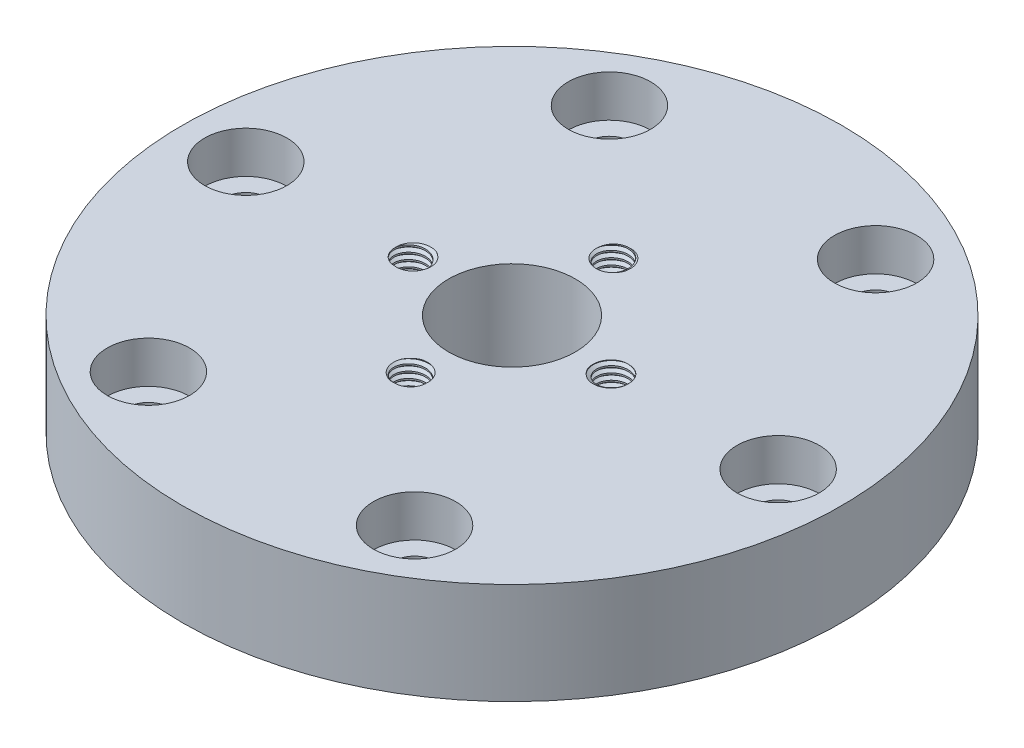
SolidWorks part; units mm, degrees
ref_plane "Front Plane" through (0, 0, 0) normal (0, 0, 1) x (1, 0, 0)
ref_plane "Top Plane" through (0, 0, 0) normal (0, 1, 0) x (1, 0, 0)
ref_plane "Right Plane" through (0, 0, 0) normal (1, 0, 0) x (0, 0, -1)
sketch "Sketch1" plane through (0, 0, 0) normal (0, 1, 0) x (1, 0, 0)
  circle A0 centre (0, 0) radius 5
  circle A1 centre (0, 0) radius 26
  dimension "D1" = 10
  dimension "D2" = 52
extrude "Boss-Extrude1" add sketch "Sketch1" along normal blind 8
sketch "Sketch2" plane through (0, 8, 0) normal (0, 1, 0) x (1, 0, 0)
  line L0 (0, 0) -> (0, 8) construction
  line L1 (0, 0) -> (-21, 0) construction
  circle A0 centre (0, 8) radius 1.25
  circle A1 centre (-21, 0) radius 1.7
  circle A2 centre (8, 0) radius 1.25
  circle A4 centre (0, -8) radius 1.25
  circle A6 centre (-8, 0) radius 1.25
  circle A8 centre (0, 21) radius 1.7 [skipped]
  circle A9 centre (21, 0) radius 1.7 [skipped]
  circle A10 centre (0, -21) radius 1.7 [skipped]
  circle A11 centre (-10.5, 18.1865) radius 1.7
  circle A12 centre (10.5, 18.1865) radius 1.7
  circle A13 centre (21, 0) radius 1.7
  circle A14 centre (10.5, -18.1865) radius 1.7
  circle A15 centre (-10.5, -18.1865) radius 1.7
  point P21 (0, 0)
  point P32 (0, 0)
  dimension "D3" = 2.5
  dimension "D4" = 3.4
  dimension "D1" = 21
  dimension "D2" = 8
  dimension "D5" = 4
  dimension "D6" = 6
extrude "Cut-Extrude1" cut sketch "Sketch2" against normal through all
sketch "Sketch3" plane through (0, 8, 0) normal (0, 1, 0) x (1, 0, 0)
  circle A0 centre (-21, 0) radius 3.25
  circle A1 centre (-10.5, 18.1865) radius 3.25
  circle A2 centre (10.5, 18.1865) radius 3.25
  circle A3 centre (21, 0) radius 3.25
  circle A4 centre (10.5, -18.1865) radius 3.25
  circle A5 centre (-10.5, -18.1865) radius 3.25
  point P15 (0, 0)
  dimension "D1" = 6.5
  dimension "D2" = 6
extrude "Cut-Extrude2" cut sketch "Sketch3" against normal blind 3.3
thread "Thread1" pitch 0.5 start angle 0, offset 1, length 0, pitch 0.5, diameter 2.5
ref_plane "Plane1" through (-1.25, 9, -8) normal (0, 0, 1) x (-1, 0, 0)
sketch "Thread Profile1" plane through (-1.25, 9, -8) normal (0, 0, 1) x (-1, 0, 0)
  line L0 (0, 0) -> (0, 0.5) construction
  line L1 (0, 0) -> (0.2706, 0.1562)
  line L2 (0.2706, 0.1562) -> (0.2706, 0.2187)
  line L3 (0.2706, 0.2187) -> (0, 0.375)
  line L4 (0.2706, 0.1875) -> (0, 0.1875) construction
  line L11 (0, 0) -> (0, 0.375)
  point P2 (0, 0)
  dimension "Pitch" = 0.5
  dimension "Profile_Angle" = 60
  dimension "Profile_Land" = 0.0625
  dimension "Profile_Height" = 0.2706
pattern_circular "CirPattern1" count 4 over 360 about axis through (0, 8, 0) along (0, -1, 0) of "Thread1"
